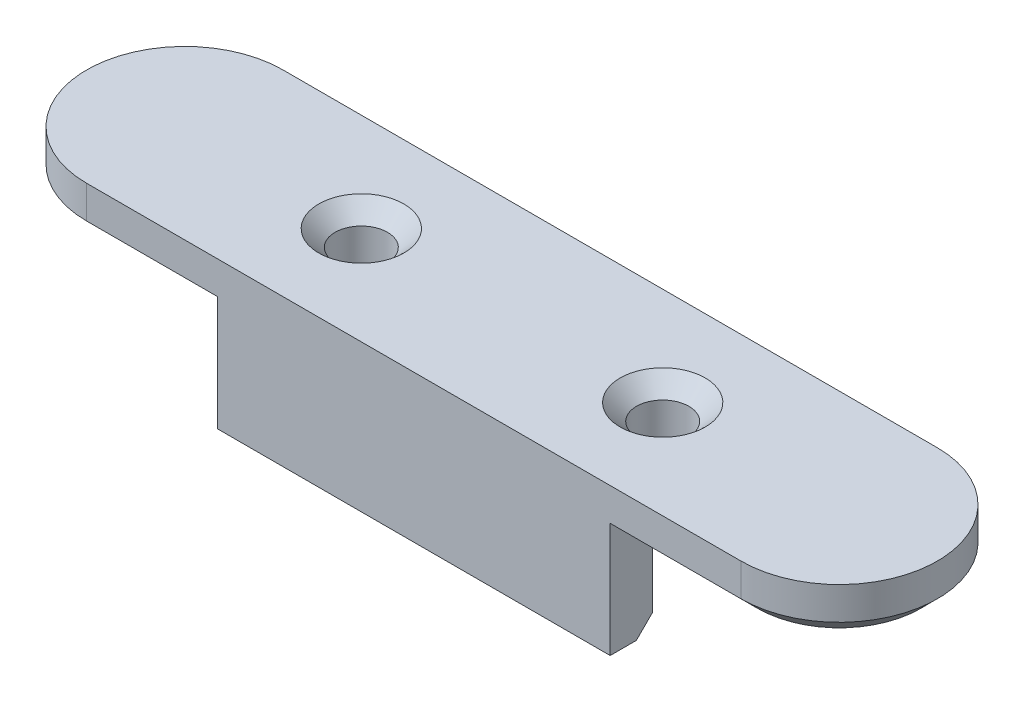
SolidWorks part; units mm, degrees
material "ABS"
ref_plane "Front Plane" through (0, 0, 0) normal (0, 0, 1) x (1, 0, 0)
ref_plane "Top Plane" through (0, 0, 0) normal (0, 1, 0) x (1, 0, 0)
ref_plane "Right Plane" through (0, 0, 0) normal (1, 0, 0) x (0, 0, -1)
sketch "Sketch1" plane through (0, 0, 0) normal (0, 1, 0) x (1, 0, 0)
  line L0 (0, 6) -> (-20, 6)
  line L2 (-20, -6) -> (0, -6)
  line L3 (0, 6) -> (0, -6)
  arc A2 (-20, -6) -> (-20, 6) centre (-20, 0) cw
  point P0 (0, 0)
  dimension "D1" = 6
  dimension "D2" = 20
extrude "Boss-Extrude1" add sketch "Sketch1" along normal blind 3
ref_axis "Axis1" through (-20, -4.1101, 0) along (0, 1, 0)
sketch "Sketch2" plane through (0, 0, 0) normal (0, 0, 1) x (1, 0, 0)
  line L0 (-20, -4.1101) -> (-20, 8.7798) construction
  line L1 (-20, 0) -> (-26, 0) construction
  line L2 (-20, 1) -> (-20, 0)
  line L3 (-20, 0) -> (-23.3166, 0)
  arc A0 (-20, 1) -> (-23.3166, 0) centre (-20, -5) ccw
  dimension "D1" = 6
  dimension "D2" = 1
revolve "Cut-Revolve1" cut sketch "Sketch2" angle 360 about axis through (-20, -4.1101, 0) along (0, 1, 0)
sketch "Sketch3" plane through (0, 0, 0) normal (0, -1, 0) x (1, 0, 0)
  line L0 (0, 6) -> (0, -6) construction
  line L1 (0, 2.9) -> (-12, 2.9)
  line L2 (0, 2.9) -> (0, -2.9)
  line L3 (0, -2.9) -> (-12, -2.9)
  line L4 (-12, 2.9) -> (-12, -2.9)
  line L5 (-20, 6) -> (0, 6) construction
  point P8 (0, 0)
  dimension "D1" = 3.1
  dimension "D2" = 12
extrude "Boss-Extrude2" [suppressed] add sketch "Sketch3" along normal blind 6
sketch "Sketch6" plane through (0, 0, 0) normal (0, -1, 0) x (1, 0, 0)
  line L1 (0, 6) -> (-12, 6)
  line L2 (0, 6) -> (0, 3.4)
  line L3 (0, 3.4) -> (-12, 3.4)
  line L4 (-12, 6) -> (-12, 3.4)
  dimension "D1" = 2.6
  dimension "D2" = 12
extrude "Boss-Extrude3" add sketch "Sketch6" along normal blind 6
mirror "Mirror2" about plane through (0, 0, 0) normal (0, 0, 1) of "Boss-Extrude3"
sketch "Sketch4" plane through (0, 0, 0) normal (0, 1, 0) x (1, 0, 0)
  circle A0 centre (-9.2106, 0) radius 1.6
  dimension "D1" = 3.2
extrude "Cut-Extrude1" cut sketch "Sketch4" against normal through all both and the other way through all
sketch "Sketch5" plane through (0, 3, 0) normal (0, 1, 0) x (1, 0, 0)
  circle A0 centre (-9.2106, 0) radius 2
  dimension "D1" = 4
extrude "Cut-Extrude2" [suppressed] cut sketch "Sketch5" against normal blind 4
chamfer "Chamfer1" distance 1 angle 45 1 edges at (-9.2106, 3, 1.6)
mirror "Mirror1" about plane through (0, 0, 0) normal (1, 0, 0) of bodies 109 110
chamfer "Chamfer2" [suppressed] distance 1 angle 45
chamfer "Chamfer3" distance 1 angle 45 8 edges at (-16, 0, -6) (-16, 0, 6) (-26, 0, 0) (16, 0, -6) (16, 0, 6) (26, 0, 0) (0, -6, -3.4) (0, -6, 3.4)
equation "\"3ю2\"=1.60701"
